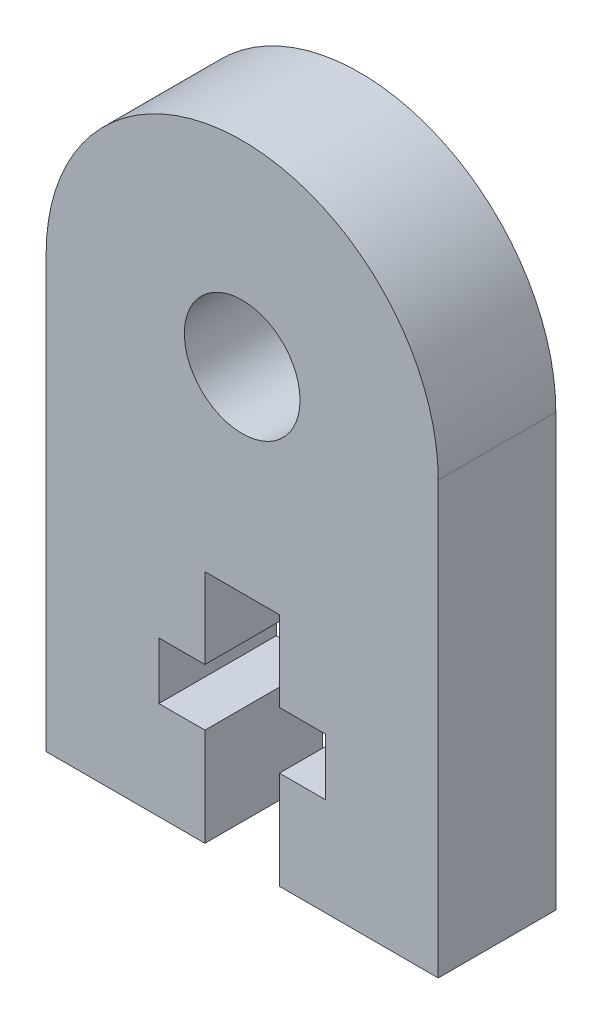
SolidWorks part; units mm, degrees
material "ABS"
ref_plane "Front Plane" through (0, 0, 0) normal (0, 0, 1) x (1, 0, 0)
ref_plane "Top Plane" through (0, 0, 0) normal (0, 1, 0) x (1, 0, 0)
ref_plane "Right Plane" through (0, 0, 0) normal (1, 0, 0) x (0, 0, -1)
sketch "Sketch1" plane through (0, 0, 0) normal (0, 0, 1) x (1, 0, 0)
  line L0 (0, 0) -> (-2.086, 2.086) construction
  line L1 (0, 0) -> (0, 2.95) construction
  line L2 (-10, 0) -> (-10, -22)
  line L3 (-10, -22) -> (10, -22)
  line L4 (10, -22) -> (10, 0)
  line L5 (0, 0) -> (0, -22) construction
  circle A0 centre (0, 0) radius 2.95
  arc A1 (-10, 0) -> (10, 0) centre (0, 0) cw
  dimension "D1" = 5.9
  dimension "D4" = 45
  dimension "D5" = 22
  dimension "D6" = 20
extrude "Boss-Extrude1" add sketch "Sketch1" along normal blind 6
sketch "Sketch3" plane through (0, 0, 6) normal (0, 0, 1) x (1, 0, 0)
  line L0 (-10, -22) -> (10, -22) construction
  line L1 (-1.9, -22) -> (1.9, -22)
  line L2 (-1.9, -22) -> (-1.9, -17)
  line L3 (-1.9, -10) -> (1.9, -10)
  line L4 (1.9, -22) -> (1.9, -17)
  line L5 (0, -10) -> (0, 0) construction
  line L6 (1.9, -14.1) -> (4.25, -14.1)
  line L7 (-4.25, -14.1) -> (-1.9, -14.1)
  line L8 (-4.25, -14.1) -> (-4.25, -17)
  line L9 (-4.25, -17) -> (-1.9, -17)
  line L10 (4.25, -14.1) -> (4.25, -17)
  line L11 (-1.9, -14.1) -> (-1.9, -10)
  line L12 (1.9, -17) -> (4.25, -17)
  line L13 (1.9, -14.1) -> (1.9, -10)
  point P18 (-3.075, -17)
  dimension "D1" = 3.8
  dimension "D3" = 12
  dimension "D4" = 8.5
  dimension "D5" = 2.9
  dimension "D6" = 5
extrude "Cut-Extrude2" cut sketch "Sketch3" against normal through all
equation "\"smallPulleyTeeth\"= 30"
equation "\"largePulleyTeeth\"= 30"
equation "\"eighthThick\"= 3.0mm"
equation "\"sixteenthThick\" = 1.7mm"
equation "\"quarterThick\"=6.0mm"
equation "\"OD\" = 145mm"
equation "\"puckAngle\" = 60.5deg"
equation "\"puckDiam\" = 76.5mm"
equation "\"axlePress\" = 5.9mm"
equation "\"D1@Sketch1\"=\"axlePress\""
equation "\"D1@Boss-Extrude1\"=\"quarterThick\""
equation "\"press\" = 0.2mm"
equation "\"wheelClear\" = 0.3mm"
equation "\"10-32clear\" = 4.8mm"
equation "\"D1@Sketch3\"=\"8-32clear\"-\"press\""
equation "\"6-32clear\" = 3.3mm"
equation "\"8-32clear\" = 4.0mm"
equation "\"wheelHeight\" = 22mm"
equation "\"D5@Sketch1\"=\"wheelHeight\""
equation "\"wheelWell\" = 65mm"
